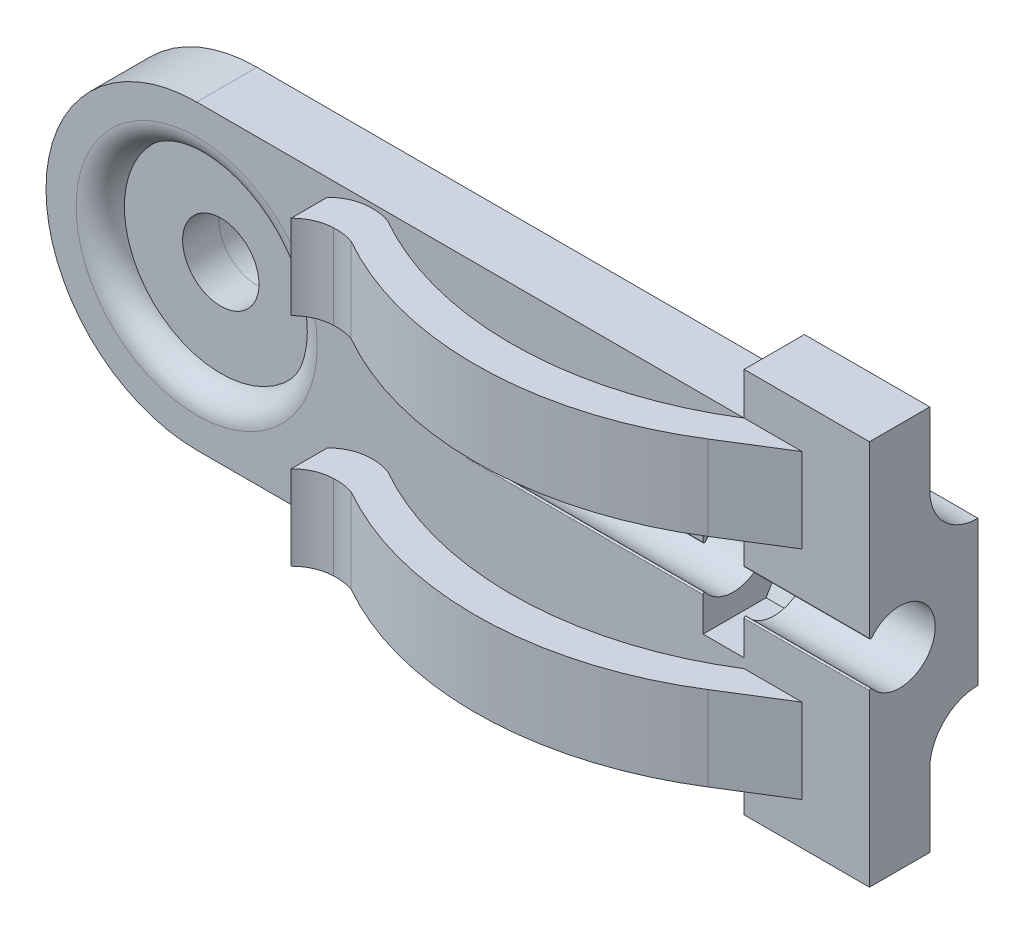
SolidWorks part; units mm, degrees
ref_plane "Front Plane" through (0, 0, 0) normal (0, 0, 1) x (1, 0, 0)
ref_plane "Top Plane" through (0, 0, 0) normal (0, 1, 0) x (1, 0, 0)
ref_plane "Right Plane" through (0, 0, 0) normal (1, 0, 0) x (0, 0, -1)
sketch "Sketch1" plane through (0, 0, 0) normal (0, 0, 1) x (1, 0, 0)
  line L0 (0, -6.25) -> (22.7, -6.25)
  line L1 (-12.7, 12.7) -> (12.7, 12.7)
  line L2 (-12.7, 12.7) -> (-12.7, -12.7)
  line L3 (-12.7, -12.7) -> (12.7, -12.7)
  line L4 (12.7, 12.7) -> (12.7, -12.7)
  line L5 (0, 6.25) -> (22.7, 6.25)
  line L6 (22.7, 6.25) -> (22.7, -6.25)
  circle A0 centre (0, 0) radius 1.5825
  arc A1 (0, 6.25) -> (0, -6.25) centre (0, 0) ccw
  dimension "D1" = 3.165
  dimension "D3" = 25.4
  dimension "D4" = 25.4
  dimension "D5" = 12.7
  dimension "D6" = 12.7
  dimension "D7" = 10
extrude "Boss-Extrude1" add sketch "Sketch1" along normal blind 2.5 contours L5 A1 L0 L4 A0 | L6 L5 L4 L0 region at (3.9827, 0, 0) region at (17.7, 0, 0)
sketch "Sketch2" plane through (0, 0, 2.5) normal (0, 0, 1) x (1, 0, 0)
  line L0 (22.7, 6.25) -> (22.7, -6.25) construction
  line L1 (22.7, -8) -> (27.9, -8)
  line L2 (22.7, -8) -> (22.7, 8)
  line L3 (22.7, 8) -> (27.9, 8)
  line L4 (27.9, -8) -> (27.9, 8)
  circle A0 centre (0, 0) radius 1.5825 construction
  dimension "D1" = 5.2
  dimension "D2" = 16
  dimension "D3" = 8
  dimension "D4" = 0
extrude "Boss-Extrude2" add sketch "Sketch2" against normal blind 2.5
sketch "Sketch3" plane through (0, 0, 2.5) normal (0, 0, 1) x (1, 0, 0)
  line L0 (22.7, 8) -> (22.7, 6.25) construction
  line L1 (22.7, 2.36) -> (21, 2.36)
  line L2 (22.7, 2.36) -> (22.7, -2.36)
  line L3 (22.7, -2.36) -> (21, -2.36)
  line L4 (21, 2.36) -> (21, -2.36)
  circle A0 centre (0, 0) radius 1.5825 construction
  dimension "D1" = 1.7
  dimension "D2" = 0
  dimension "D3" = 4.72
  dimension "D4" = 2.36
extrude "Cut-Extrude1" cut sketch "Sketch3" against normal through all
sketch "Sketch7" plane through (0, -6.25, 0) normal (0, -1, 0) x (1, 0, 0)
  line L1 (6.1299, 3.2107) -> (6.1299, 4.7107)
  line L3 (22.7, 4) -> (22.7, 2.5)
  arc A0 (22.7, 2.5) -> (8.2067, 2.7997) centre (15.2027, -9.4701) ccw
  arc A1 (7.3606, 2.6809) -> (6.1299, 3.2107) centre (7.409, 4.4878) cw
  arc A2 (7.3606, 2.6809) -> (8.2067, 2.7997) centre (7.4758, 4.9321) ccw
  arc A3 (7.3606, 4.1809) -> (6.1299, 4.7107) centre (7.409, 5.9878) cw
  arc A4 (22.7, 4) -> (8.2067, 4.2997) centre (15.2027, -7.9701) ccw
  arc A5 (7.3606, 4.1809) -> (8.2067, 4.2997) centre (7.4758, 6.4321) ccw
  dimension "D3" = 2
  dimension "D1" = 1.5
extrude "Boss-Extrude3" add sketch "Sketch7" against normal blind 3.5 separate body
sketch "Sketch9" plane through (0, -6.25, 0) normal (0, -1, 0) x (1, 0, 0)
  line L0 (22.7, 4) -> (25.1049, 2.5)
  line L1 (25.1049, 2.5) -> (22.7, 2.5)
  line L2 (22.7, 2.5) -> (22.7, 4)
extrude "Boss-Extrude5" add sketch "Sketch9" against normal blind 3.5 separate body
combine bodies "Combine1" operation type add bodies to combine 111 106
ref_plane "Plane1" through (0, 0, 0) normal (0, -1, 0) x (-1, 0, 0)
mirror "Mirror5" about plane through (0, 0, 0) normal (0, -1, 0) of bodies 112
combine bodies "Combine4" operation type add bodies to combine 103 112 116
sketch "Sketch10" plane through (0, 0, 0) normal (0, 0, -1) x (-1, 0, 0)
  circle A0 centre (0, 0) radius 4
  dimension "D1" = 8
extrude "Boss-Extrude6" add sketch "Sketch10" along normal blind 1.875
sketch "Sketch11" plane through (0, 0, 0) normal (0, 0, 1) x (1, 0, 0)
  circle A0 centre (0, 0) radius 1.585
  dimension "D1" = 3.17
extrude "Cut-Extrude4" cut sketch "Sketch11" against normal through all
sketch "Sketch12" plane through (0, 0, 2.5) normal (0, 0, 1) x (1, 0, 0)
  circle A0 centre (0, 0) radius 4
  dimension "D1" = 8
extrude "Cut-Extrude5" cut sketch "Sketch12" against normal blind 1
fillet "Fillet1" radius 1 1 edges at (4, 0, 2.5)
fillet "Fillet2" radius 1 1 edges at (-4, 0, -1.875)
sketch "Sketch14" plane through (0, 0, 0) normal (0, 0, -1) x (-1, 0, 0)
  line L0 (-27.9, -8) -> (-27.9, 8) construction
  line L1 (-27.9, -3) -> (-16.2292, -3)
  line L2 (-27.9, -3) -> (-27.9, 3)
  line L3 (-27.9, 3) -> (-16.2292, 3)
  line L4 (-16.2292, -3) -> (-16.2292, 3)
  line L5 (0, -6.25) -> (-22.7, -6.25) construction
  dimension "D1" = 6
  dimension "D2" = 3.25
extrude "Boss-Extrude7" add sketch "Sketch14" along normal blind 2
sketch "Sketch6" plane through (27.9, 0, 0) normal (1, 0, 0) x (0, 0, -1)
  line L0 (-2.5, -8) -> (-2.5, 8) construction
  line L1 (0, -8) -> (-2.5, -8) construction
  line L2 (0, 8) -> (-2.5, 8) construction
  circle A0 centre (-1.25, 0) radius 1.475
  point P6 (-1.25, 8)
  dimension "D4" = 2.95
  dimension "D1" = 1.25
  dimension "D2" = 8
  dimension "D3" = 8
extrude "Cut-Extrude3" cut sketch "Sketch6" against normal blind 16.7
sketch "Sketch16" plane through (21, 0, 0) normal (1, 0, 0) x (0, 0, -1)
  line L1 (1.4751, 0) -> (0.1125, 2.36)
  line L2 (0.1125, 2.36) -> (-2.6125, 2.36)
  line L3 (-2.6125, 2.36) -> (-3.9751, 0)
  line L4 (-3.9751, 0) -> (-2.6125, -2.36)
  line L5 (-2.6125, -2.36) -> (0.1125, -2.36)
  line L6 (0.1125, -2.36) -> (1.4751, 0)
  circle A0 centre (-1.25, 0) radius 2.36 construction
extrude "Cut-Extrude8" cut sketch "Sketch16" along normal up to surface (1.7 mm away) up to face at (22.7, -1.7445, 1.25)
fillet "Fillet3" radius 2 2 edges at (22.0646, -3, 0) (22.0646, 3, 0)
fillet "Fillet4" radius 0.05 6 edges at (25.3, 0.783, 2.5) (25.3, -0.783, 2.5) (13.7146, 0.783, 0) (13.7146, -0.783, 0) (16.1, 0.783, 2.5) (16.1, -0.783, 2.5)
